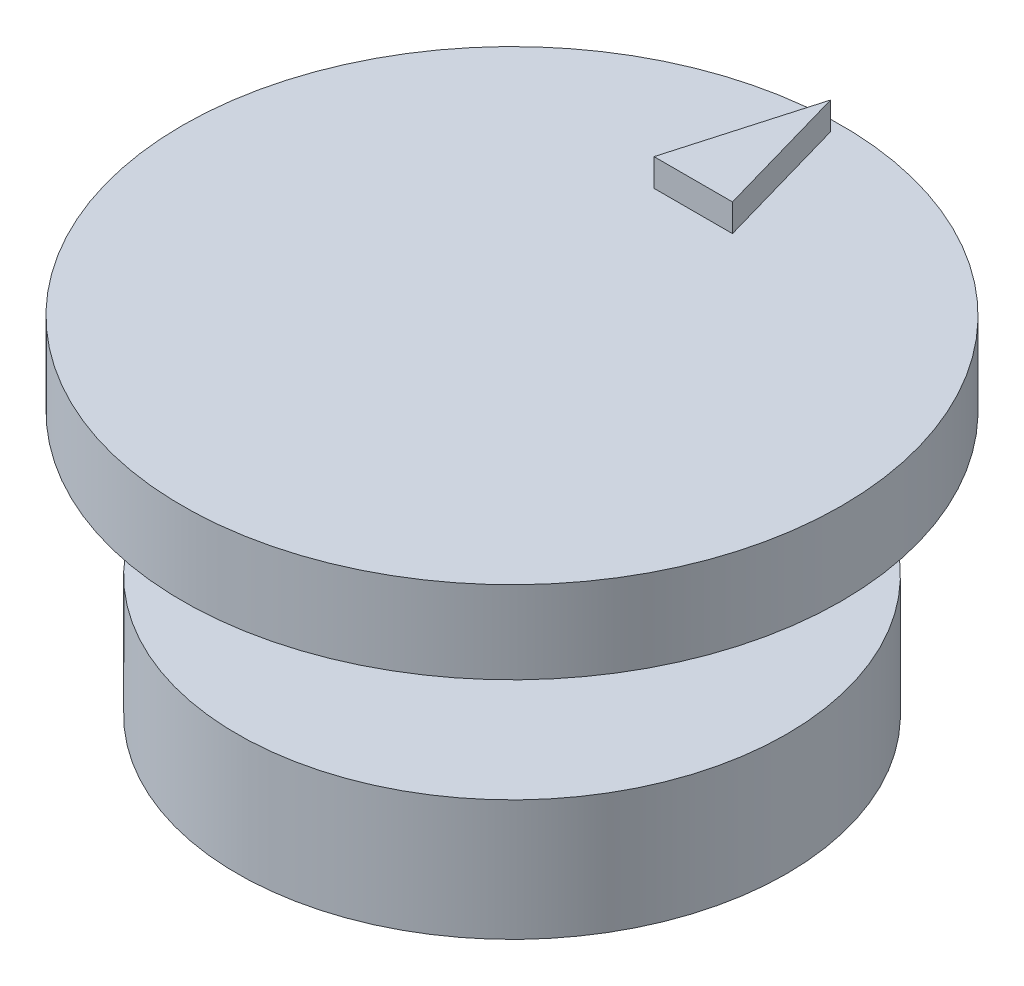
SolidWorks part; units mm, degrees
ref_plane "Front Plane" through (0, 0, 0) normal (0, 0, 1) x (1, 0, 0)
ref_plane "Top Plane" through (0, 0, 0) normal (0, 1, 0) x (1, 0, 0)
ref_plane "Right Plane" through (0, 0, 0) normal (1, 0, 0) x (0, 0, -1)
sketch "Sketch1" plane through (0, 0, 0) normal (0, 0, 1) x (1, 0, 0)
  line L0 (0, -20.8911) -> (0, -36.8931)
  line L1 (0, -36.8931) -> (12.7, -36.8931)
  line L2 (12.7, -36.8931) -> (12.7, -31.3051)
  line L3 (12.7, -31.3051) -> (3.175, -31.3051)
  line L4 (3.175, -31.3051) -> (3.175, -26.2251)
  line L5 (3.175, -26.2251) -> (12.7, -26.2251)
  line L6 (12.7, -26.2251) -> (12.7, -24.7011)
  line L7 (12.7, -24.7011) -> (15.24, -24.7011)
  line L8 (15.24, -24.7011) -> (15.24, -20.8911)
  line L9 (15.24, -20.8911) -> (0, -20.8911)
  dimension "D1" = 3.175
  dimension "D2" = 9.525
  dimension "D3" = 5.08
  dimension "D4" = 5.588
  dimension "D5" = 1.524
  dimension "D6" = 3.81
  dimension "D7" = 12.7
  dimension "D8" = 15.24
revolve "dial base shape" add sketch "Sketch1" angle 360 about L0
sketch "Sketch2" plane through (0, -20.8911, 0) normal (0, 1, 0) x (1, 0, 0)
  line L0 (0, 14.732) -> (-1.8139, 8.382)
  line L1 (-1.8139, 8.382) -> (1.8139, 8.382)
  line L2 (1.8139, 8.382) -> (0, 14.732)
  dimension "D1" = 6.35
  dimension "D2" = 8.382
  dimension "D3" = 6.604
  dimension "D4" = 6.604
extrude "arrow" add sketch "Sketch2" along normal blind 1.27
sketch "Sketch3" plane through (0, -36.8931, 0) normal (0, -1, 0) x (1, 0, 0)
  circle A0 centre (0, -9.8549) radius 2.286
  dimension "D1" = 4.572
extrude "flag" add sketch "Sketch3" along normal blind 2.54
fillet "Fillet1" radius 1.27 1 edges at (-2.286, -36.8931, -9.8549)
